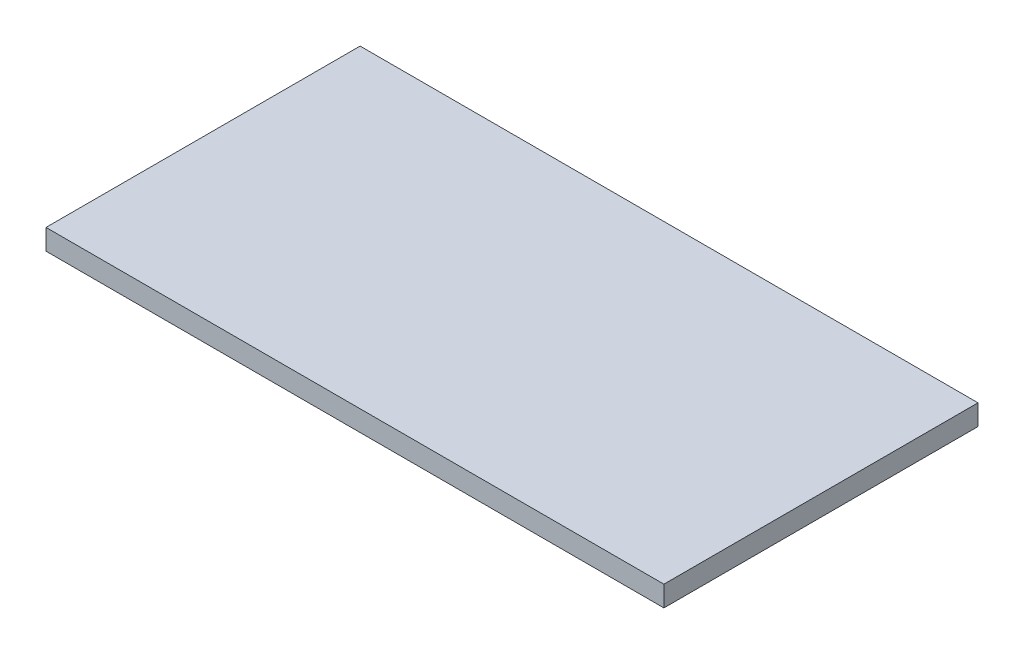
SolidWorks part; units mm, degrees
ref_plane "Ebene vorne" through (0, 0, 0) normal (0, 0, 1) x (1, 0, 0)
ref_plane "Ebene oben" through (0, 0, 0) normal (0, 1, 0) x (1, 0, 0)
ref_plane "Ebene rechts" through (0, 0, 0) normal (1, 0, 0) x (0, 0, -1)
sketch "Sketch1" plane through (0, 0, 0) normal (0, 1, 0) x (1, 0, 0)
  line L0 (-24.1206, 0) -> (93.4673, 0) construction
  line L2 (0, 30.5) -> (120, 30.5)
  line L3 (0, 30.5) -> (0, -30.5)
  line L4 (0, -30.5) -> (120, -30.5)
  line L5 (120, 30.5) -> (120, -30.5)
  dimension "D1" = 61
  dimension "D2" = 120
extrude "Boss-Extrude1" add sketch "Sketch1" along normal blind 4
